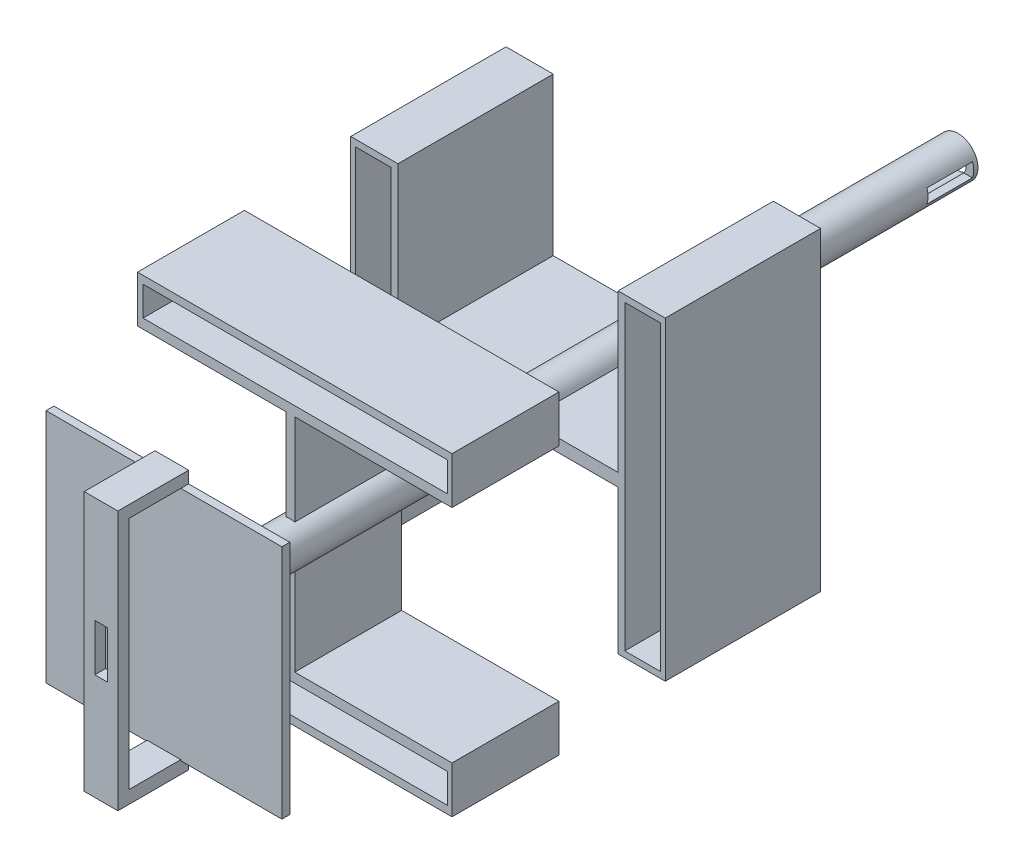
SolidWorks part; units mm, degrees
ref_plane "Front Plane" through (0, 0, 0) normal (0, 0, 1) x (1, 0, 0)
ref_plane "Top Plane" through (0, 0, 0) normal (0, 1, 0) x (1, 0, 0)
ref_plane "Right Plane" through (0, 0, 0) normal (1, 0, 0) x (0, 0, -1)
sketch "Sketch1" plane through (0, 0, 0) normal (0, 0, 1) x (1, 0, 0)
  circle A0 centre (0, 0) radius 12.6378
extrude "Boss-Extrude1" add sketch "Sketch1" along normal blind 175 and the other way blind 325
sketch "Sketch2" plane through (0, 0, 0) normal (0, 1, 0) x (1, 0, 0)
  line L1 (-2.8188, -99.6423) -> (2.8188, -99.6423)
  line L2 (-2.8188, -99.6423) -> (-2.8188, -31.6586)
  line L3 (-2.8188, -31.6586) -> (2.8188, -31.6586)
  line L4 (2.8188, -99.6423) -> (2.8188, -31.6586)
  line L5 (-2.8188, -99.6423) -> (2.8188, -31.6586) construction
  line L6 (-2.8188, -31.6586) -> (2.8188, -99.6423) construction
  point P0 (0, -65.6505)
extrude "Boss-Extrude2" add sketch "Sketch2" along normal blind 100 and the other way blind 100
ref_plane "Plane1" through (0, 0, 0) normal (0, 1, 0) x (1, 0, 0)
sketch "Sketch3" plane through (2.8188, 0, 0) normal (1, 0, 0) x (0, 0, -1)
  line L0 (-31.6586, 12.3195) -> (-31.6586, 100) construction
  line L1 (-99.6423, 100) -> (-31.6586, 100)
  line L2 (-99.6423, 100) -> (-99.6423, 70.305)
  line L3 (-99.6423, 70.305) -> (-31.6586, 70.305)
  line L4 (-31.6586, 100) -> (-31.6586, 70.305)
  line L5 (37.391, 0) -> (-37.391, 0) construction
  line L6 (-99.6423, -70.305) -> (-31.6586, -70.305)
  line L7 (-31.6586, -100) -> (-31.6586, -70.305)
  line L8 (-99.6423, -100) -> (-31.6586, -100)
  line L9 (-99.6423, -100) -> (-99.6423, -70.305)
extrude "Boss-Extrude3" add sketch "Sketch3" along normal blind 100 and the other way blind 100
sketch "Sketch4" plane through (0, 0, 99.6423) normal (0, 0, 1) x (1, 0, 0)
  line L0 (37.391, 0) -> (-37.391, 0) construction
  line L1 (-93.6687, 95.1241) -> (99.8485, 95.1241)
  line L2 (-93.6687, 95.1241) -> (-93.6687, 76.4229)
  line L3 (-93.6687, 76.4229) -> (99.8485, 76.4229)
  line L4 (99.8485, 95.1241) -> (99.8485, 76.4229)
  line L5 (-93.6687, -76.4229) -> (99.8485, -76.4229)
  line L6 (99.8485, -95.1241) -> (99.8485, -76.4229)
  line L7 (-93.6687, -95.1241) -> (99.8485, -95.1241)
  line L8 (-93.6687, -95.1241) -> (-93.6687, -76.4229)
extrude "Cut-Extrude1" cut sketch "Sketch4" against normal blind 63
sketch "Sketch5" plane through (0, 0, 0) normal (1, 0, 0) x (0, 0, -1)
  line L0 (0, 0) -> (-50000, 0) construction
  line L3 (137.5269, -4.0497) -> (38.7674, -4.0497)
  line L4 (137.5269, -4.0497) -> (137.5269, 4.0497)
  line L5 (137.5269, 4.0497) -> (38.7674, 4.0497)
  line L6 (38.7674, -4.0497) -> (38.7674, 4.0497)
  line L7 (137.5269, -4.0497) -> (38.7674, 4.0497) construction
  line L8 (137.5269, 4.0497) -> (38.7674, -4.0497) construction
  point P2 (88.1471, 0)
extrude "Boss-Extrude4" add sketch "Sketch5" along normal blind 100 and the other way blind 100
ref_plane "Plane2" through (0, 0, 0) normal (-1, 0, 0) x (0, 0, 1)
sketch "Sketch6" plane through (0, 4.0497, 0) normal (0, 1, 0) x (1, 0, 0)
  line L0 (-100, 38.7674) -> (-11.9714, 38.7674) construction
  line L1 (-100, 137.5269) -> (-70, 137.5269)
  line L2 (-100, 137.5269) -> (-100, 38.7674)
  line L3 (-100, 38.7674) -> (-70, 38.7674)
  line L4 (-70, 137.5269) -> (-70, 38.7674)
  line L5 (0, 54.3177) -> (0, -54.3177) construction
  line L6 (100, 38.7674) -> (70, 38.7674)
  line L7 (70, 137.5269) -> (70, 38.7674)
  line L8 (100, 137.5269) -> (70, 137.5269)
  line L9 (100, 137.5269) -> (100, 38.7674)
  dimension "D1" = 30
extrude "Boss-Extrude5" add sketch "Sketch6" along normal blind 100 and the other way blind 100
sketch "Sketch7" plane through (0, 0, -38.7674) normal (0, 0, 1) x (1, 0, 0)
  line L0 (0, 54.3177) -> (0, -54.3177) construction
  line L1 (-96.9063, 99.8524) -> (-74.2711, 99.8524)
  line L2 (-96.9063, 99.8524) -> (-96.9063, -92.0924)
  line L3 (-96.9063, -92.0924) -> (-74.2711, -92.0924)
  line L4 (-74.2711, 99.8524) -> (-74.2711, -92.0924)
  line L5 (96.9063, -92.0924) -> (74.2711, -92.0924)
  line L6 (74.2711, 99.8524) -> (74.2711, -92.0924)
  line L7 (96.9063, 99.8524) -> (74.2711, 99.8524)
  line L8 (96.9063, 99.8524) -> (96.9063, -92.0924)
extrude "Cut-Extrude2" cut sketch "Sketch7" against normal blind 86
sketch "Sketch8" plane through (0, 0, 175) normal (0, 0, 1) x (1, 0, 0)
  line L1 (75, -75) -> (-75, -75)
  line L2 (75, -75) -> (75, 75)
  line L3 (75, 75) -> (-75, 75)
  line L4 (-75, -75) -> (-75, 75)
  line L5 (75, -75) -> (-75, 75) construction
  line L6 (75, 75) -> (-75, -75) construction
  point P0 (0, 0)
  dimension "D1" = 150
  dimension "D2" = 150
extrude "Boss-Extrude6" add sketch "Sketch8" along normal blind 5
ref_plane "Plane3" through (0, 0, 220) normal (0, 0, 1) x (1, 0, 0)
sketch "Sketch10" plane through (0, 0, 220) normal (0, 0, 1) x (1, 0, 0)
  line L1 (-10.6983, -82.5526) -> (10.6983, -82.5526)
  line L2 (-10.6983, -82.5526) -> (-10.6983, 82.5526)
  line L3 (-10.6983, 82.5526) -> (10.6983, 82.5526)
  line L4 (10.6983, -82.5526) -> (10.6983, 82.5526)
  line L5 (-10.6983, -82.5526) -> (10.6983, 82.5526) construction
  line L6 (-10.6983, 82.5526) -> (10.6983, -82.5526) construction
  point P0 (0, 0)
extrude "Boss-Extrude7" add sketch "Sketch10" against normal up to surface (45 mm away) up to face at (12.6378, 0, 175)
sketch "Sketch11" plane through (-10.6983, 0, 0) normal (-1, 0, 0) x (0, 0, 1)
  line L0 (180, 75) -> (180, -75) construction
  line L1 (180, 75) -> (213.0621, 75)
  line L2 (180, 75) -> (180, -74.3722)
  line L3 (180, -74.3722) -> (213.0621, -74.3722)
  line L4 (213.0621, 75) -> (213.0621, -74.3722)
extrude "Cut-Extrude3" cut sketch "Sketch11" against normal blind 40
sketch "Sketch12" plane through (0, 0, 220) normal (0, 0, 1) x (1, 0, 0)
  line L1 (4, -15) -> (-4, -15)
  line L2 (4, -15) -> (4, 15)
  line L3 (4, 15) -> (-4, 15)
  line L4 (-4, -15) -> (-4, 15)
  line L5 (4, -15) -> (-4, 15) construction
  line L6 (4, 15) -> (-4, -15) construction
  point P0 (0, 0)
  dimension "D1" = 8
  dimension "D2" = 30
extrude "Cut-Extrude4" cut sketch "Sketch12" against normal blind 30
sketch "Sketch13" plane through (0, 0, -325) normal (0, 0, -1) x (-1, 0, 0)
  circle A0 centre (0, 0) radius 7.8436
extrude "Cut-Extrude5" cut sketch "Sketch13" against normal blind 141
sketch "Sketch14" plane through (0, 0, 0) normal (-1, 0, 0) x (0, 0, 1)
  line L1 (-322.2745, -4.6084) -> (-293.2745, -4.6084)
  line L2 (-322.2745, -4.6084) -> (-322.2745, 4.3916)
  line L3 (-322.2745, 4.3916) -> (-293.2745, 4.3916)
  line L4 (-293.2745, -4.6084) -> (-293.2745, 4.3916)
  line L5 (-322.2745, -4.6084) -> (-293.2745, 4.3916) construction
  line L6 (-322.2745, 4.3916) -> (-293.2745, -4.6084) construction
  line L7 (-281.6408, -4.6084) -> (-256.6408, -4.6084)
  line L8 (-281.6408, -4.6084) -> (-281.6408, 4.3916)
  line L9 (-281.6408, 4.3916) -> (-256.6408, 4.3916)
  line L10 (-256.6408, -4.6084) -> (-256.6408, 4.3916)
  line L11 (-281.6408, -4.6084) -> (-256.6408, 4.3916) construction
  line L12 (-281.6408, 4.3916) -> (-256.6408, -4.6084) construction
  point P0 (-307.7745, -0.1084)
  point P5 (-269.1408, -0.1084)
  point P10 (0, 0)
  point P11 (0, 0)
  dimension "D1" = 29
  dimension "D2" = 9
  dimension "D3" = 25
  dimension "D4" = 9
extrude "Cut-Extrude6" cut sketch "Sketch14" against normal blind 141 contours L1 L4 L3 L2
sketch "Sketch15" plane through (0, 0, 0) normal (-1, 0, 0) x (0, 0, 1)
  line L1 (-289.0199, -4.5638) -> (-260.0199, -4.5638)
  line L2 (-289.0199, -4.5638) -> (-289.0199, 4.4362)
  line L3 (-289.0199, 4.4362) -> (-260.0199, 4.4362)
  line L4 (-260.0199, -4.5638) -> (-260.0199, 4.4362)
  line L5 (-289.0199, -4.5638) -> (-260.0199, 4.4362) construction
  line L6 (-289.0199, 4.4362) -> (-260.0199, -4.5638) construction
  point P0 (-274.5199, -0.0638)
  dimension "D1" = 29
  dimension "D2" = 9
extrude "Cut-Extrude7" cut sketch "Sketch15" along normal blind 83
